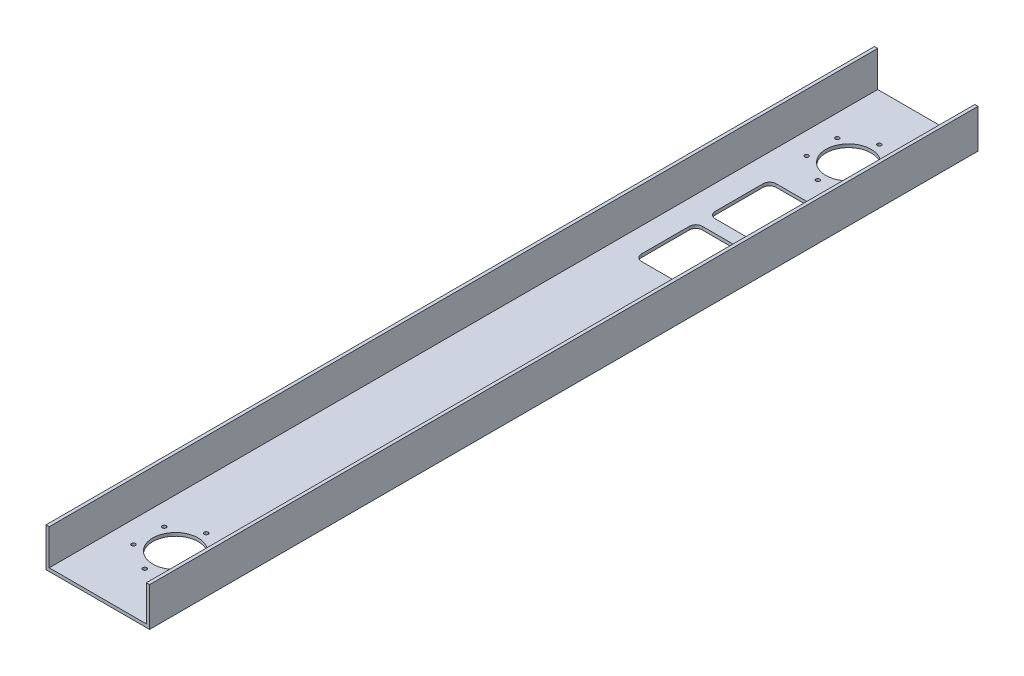
SolidWorks part; units mm, degrees
ref_plane "Front" through (0, 0, 0) normal (0, 0, 1) x (1, 0, 0)
ref_plane "Top" through (0, 0, 0) normal (0, 1, 0) x (1, 0, 0)
ref_plane "Right" through (0, 0, 0) normal (1, 0, 0) x (0, 0, -1)
sketch "Sketch1" plane through (0, 0, 0) normal (0, 0, 1) x (1, 0, 0)
  line L0 (3.175, 3.175) -> (3.175, 38.1)
  line L1 (0, 0) -> (101.6, 0)
  line L2 (0, 0) -> (0, 38.1)
  line L4 (101.6, 0) -> (101.6, 38.1)
  line L5 (3.175, 3.175) -> (98.425, 3.175)
  line L6 (98.425, 3.175) -> (98.425, 38.1)
  line L7 (0, 38.1) -> (3.175, 38.1)
  line L8 (101.6, 38.1) -> (98.425, 38.1)
  dimension "D1" = 38.1
  dimension "D2" = 101.6
  dimension "D3" = 3.175
extrude "Boss-Extrude1" add sketch "Sketch1" along normal blind 812.8
sketch "Sketch2" plane through (0, 0, 0) normal (0, -1, 0) x (1, 0, 0)
  line L0 (50.8, 812.8) -> (50.8, 736.6) construction
  line L1 (0, 812.8) -> (101.6, 812.8) construction
  circle A0 centre (50.8, 736.6) radius 22.2377
  dimension "D2" = 44.4754
  dimension "D1" = 76.2
extrude "Cut-Extrude1" cut sketch "Sketch2" against normal up to next
sketch "Sketch3" plane through (0, 0, 0) normal (0, -1, 0) x (1, 0, 0)
  line L0 (50.8, 736.6) -> (50.8, 766.7625) construction
  circle A0 centre (50.8, 766.7625) radius 1.8987
  circle A1 centre (76.9215, 751.6813) radius 1.8987
  circle A2 centre (76.9215, 721.5187) radius 1.8986
  circle A3 centre (50.8, 706.4375) radius 1.8986
  circle A4 centre (24.6785, 721.5187) radius 1.8987
  circle A5 centre (24.6785, 751.6812) radius 1.8987
  circle A6 centre (50.8, 736.6) radius 22.2377 construction
  point P17 (50.8, 736.6)
  dimension "D2" = 3.7973
  dimension "D1" = 30.1625
  dimension "D3" = 6
extrude "Cut-Extrude2" cut sketch "Sketch3" against normal up to next
ref_plane "Mid_Plane" through (0, 0, 406.4) normal (0, 0, 1) x (1, 0, 0)
mirror "Mirror1" about plane through (0, 0, 406.4) normal (0, 0, 1) of "Cut-Extrude2", "Cut-Extrude1"
sketch "Sketch4" plane through (0, 0, 0) normal (0, -1, 0) x (1, 0, 0)
  line L0 (26.9875, 149.3128) -> (0, 149.3128) construction
  line L3 (68.2625, 129.8363) -> (33.3375, 129.8363)
  line L4 (74.6125, 136.1863) -> (74.6125, 183.2)
  line L5 (68.2625, 261.9637) -> (33.3375, 261.9637)
  line L6 (26.9875, 136.1863) -> (26.9875, 183.2)
  line L7 (0, 812.8) -> (0, 0) construction
  line L8 (74.6125, 247.0656) -> (101.6, 247.0656) construction
  line L9 (101.6, 812.8) -> (101.6, 0) construction
  line L11 (33.3375, 189.55) -> (68.2625, 189.55)
  line L12 (33.3375, 202.25) -> (68.2625, 202.25)
  line L13 (26.9875, 208.6) -> (26.9875, 255.6137)
  line L14 (74.6125, 208.6) -> (74.6125, 255.6137)
  arc A0 (33.3375, 261.9637) -> (26.9875, 255.6137) centre (33.3375, 255.6137) ccw
  arc A1 (74.6125, 255.6137) -> (68.2625, 261.9637) centre (68.2625, 255.6137) ccw
  arc A2 (68.2625, 129.8363) -> (74.6125, 136.1863) centre (68.2625, 136.1863) ccw
  arc A3 (33.3375, 129.8363) -> (26.9875, 136.1863) centre (33.3375, 136.1863) cw
  arc A4 (33.3375, 202.25) -> (26.9875, 208.6) centre (33.3375, 208.6) cw
  arc A5 (68.2625, 202.25) -> (74.6125, 208.6) centre (68.2625, 208.6) ccw
  arc A6 (68.2625, 189.55) -> (74.6125, 183.2) centre (68.2625, 183.2) cw
  arc A7 (33.3375, 189.55) -> (26.9875, 183.2) centre (33.3375, 183.2) ccw
  dimension "D1" = 6.35
  dimension "D2" = 47.625
extrude "Cut-Extrude3" cut sketch "Sketch4" against normal up to next
